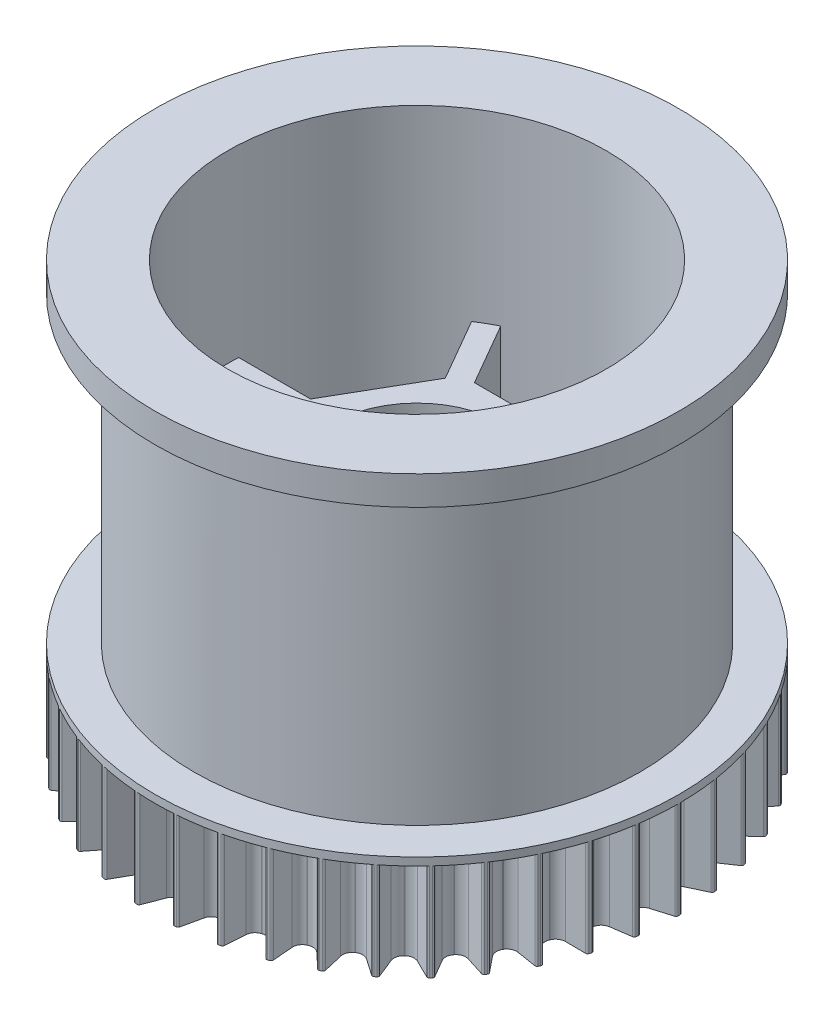
SolidWorks part; units mm, degrees
ref_plane "前视基准面" through (0, 0, 0) normal (0, 0, 1) x (1, 0, 0)
ref_plane "上视基准面" through (0, 0, 0) normal (0, 1, 0) x (1, 0, 0)
ref_plane "右视基准面" through (0, 0, 0) normal (1, 0, 0) x (0, 0, -1)
other "Configuration Table"
sketch "草图1" plane through (0, 0, 0) normal (0, 1, 0) x (1, 0, 0)
  line L0 (0, 0) -> (7.9279, 0) construction
  line L1 (0, 0) -> (0, 4.4256) construction
  line L2 (12.4216, 0.4494) -> (13.4287, 0.1463)
  line L3 (12.4216, -0.4494) -> (13.4287, -0.1463)
  line L4 (12.2159, -2.2957) -> (13.2569, -2.1461)
  line L5 (12.3499, -1.407) -> (13.3005, -1.8568)
  line L6 (11.7373, -4.0908) -> (12.789, -4.098)
  line L7 (12.0023, -3.2319) -> (12.8752, -3.8184)
  line L8 (10.9965, -5.7945) -> (12.0354, -5.9583)
  line L9 (11.3865, -4.9846) -> (12.1623, -5.6947)
  line L10 (10.0101, -7.3687) -> (11.0129, -7.6855)
  line L11 (10.5164, -6.626) -> (11.1777, -7.4438)
  line L12 (8.8, -8.7783) -> (9.7445, -9.2411)
  line L13 (9.4114, -8.1194) -> (9.9434, -9.0266)
  line L14 (7.3934, -9.9918) -> (8.2583, -10.5902)
  line L15 (8.0961, -9.4314) -> (8.487, -10.4078)
  line L16 (5.8216, -10.9822) -> (6.5877, -11.7028)
  line L17 (6.6, -10.5328) -> (6.841, -11.5565)
  line L18 (4.1198, -11.7272) -> (4.7699, -12.5539)
  line L19 (4.9565, -11.3988) -> (5.0422, -12.447)
  line L20 (2.3259, -12.2102) -> (2.8456, -13.1246)
  line L21 (3.2022, -12.0102) -> (3.1308, -13.0595)
  line L22 (0.4801, -12.4205) -> (0.8577, -13.4021)
  line L23 (1.3764, -12.3533) -> (1.1494, -13.3802)
  line L24 (-1.3764, -12.3533) -> (-1.1494, -13.3802)
  line L25 (-0.4801, -12.4205) -> (-0.8577, -13.4021)
  line L26 (-3.2022, -12.0102) -> (-3.1308, -13.0595)
  line L27 (-2.3259, -12.2102) -> (-2.8456, -13.1246)
  line L28 (-4.9565, -11.3988) -> (-5.0422, -12.447)
  line L29 (-4.1198, -11.7272) -> (-4.7699, -12.5539)
  line L30 (-6.6, -10.5328) -> (-6.841, -11.5565)
  line L31 (-5.8216, -10.9822) -> (-6.5877, -11.7028)
  line L32 (-8.0961, -9.4314) -> (-8.487, -10.4078)
  line L33 (-7.3934, -9.9918) -> (-8.2583, -10.5902)
  line L34 (-9.4114, -8.1194) -> (-9.9434, -9.0266)
  line L35 (-8.8, -8.7783) -> (-9.7445, -9.2411)
  line L36 (-10.5164, -6.626) -> (-11.1777, -7.4438)
  line L37 (-10.0101, -7.3687) -> (-11.0129, -7.6855)
  line L38 (-11.3865, -4.9846) -> (-12.1623, -5.6947)
  line L39 (-10.9965, -5.7945) -> (-12.0354, -5.9583)
  line L40 (-12.0023, -3.2319) -> (-12.8752, -3.8184)
  line L41 (-11.7373, -4.0908) -> (-12.789, -4.098)
  line L42 (-12.3499, -1.407) -> (-13.3005, -1.8568)
  line L43 (-12.2159, -2.2957) -> (-13.2569, -2.1461)
  line L44 (-12.4216, 0.4494) -> (-13.4287, 0.1463)
  line L45 (-12.4216, -0.4494) -> (-13.4287, -0.1463)
  line L46 (-12.2159, 2.2957) -> (-13.2569, 2.1461)
  line L47 (-12.3499, 1.407) -> (-13.3005, 1.8568)
  line L48 (-11.7373, 4.0908) -> (-12.789, 4.098)
  line L49 (-12.0023, 3.2319) -> (-12.8752, 3.8184)
  line L50 (-10.9965, 5.7945) -> (-12.0354, 5.9583)
  line L51 (-11.3865, 4.9846) -> (-12.1623, 5.6947)
  line L52 (-10.0101, 7.3687) -> (-11.0129, 7.6855)
  line L53 (-10.5164, 6.626) -> (-11.1777, 7.4438)
  line L54 (-8.8, 8.7783) -> (-9.7445, 9.2411)
  line L55 (-9.4114, 8.1194) -> (-9.9434, 9.0266)
  line L56 (-7.3934, 9.9918) -> (-8.2583, 10.5902)
  line L57 (-8.0961, 9.4314) -> (-8.487, 10.4078)
  line L58 (-5.8216, 10.9822) -> (-6.5877, 11.7028)
  line L59 (-6.6, 10.5328) -> (-6.841, 11.5565)
  line L60 (-4.1198, 11.7272) -> (-4.7699, 12.5539)
  line L61 (-4.9565, 11.3988) -> (-5.0422, 12.447)
  line L62 (-2.3259, 12.2102) -> (-2.8456, 13.1246)
  line L63 (-3.2022, 12.0102) -> (-3.1308, 13.0595)
  line L64 (-0.4801, 12.4205) -> (-0.8577, 13.4021)
  line L65 (-1.3764, 12.3533) -> (-1.1494, 13.3802)
  line L66 (1.3764, 12.3533) -> (1.1494, 13.3802)
  line L67 (0.4801, 12.4205) -> (0.8577, 13.4021)
  line L68 (3.2022, 12.0102) -> (3.1308, 13.0595)
  line L69 (2.3259, 12.2102) -> (2.8456, 13.1246)
  line L70 (4.9565, 11.3988) -> (5.0422, 12.447)
  line L71 (4.1198, 11.7272) -> (4.7699, 12.5539)
  line L72 (6.6, 10.5328) -> (6.841, 11.5565)
  line L73 (5.8216, 10.9822) -> (6.5877, 11.7028)
  line L74 (8.0961, 9.4314) -> (8.487, 10.4078)
  line L75 (7.3934, 9.9918) -> (8.2583, 10.5902)
  line L76 (9.4114, 8.1194) -> (9.9434, 9.0266)
  line L77 (8.8, 8.7783) -> (9.7445, 9.2411)
  line L78 (10.5164, 6.626) -> (11.1777, 7.4438)
  line L79 (10.0101, 7.3687) -> (11.0129, 7.6855)
  line L80 (11.3865, 4.9846) -> (12.1623, 5.6947)
  line L81 (10.9965, 5.7945) -> (12.0354, 5.9583)
  line L82 (12.0023, 3.2319) -> (12.8752, 3.8184)
  line L83 (11.7373, 4.0908) -> (12.789, 4.098)
  line L84 (12.3499, 1.407) -> (13.3005, 1.8568)
  line L85 (12.2159, 2.2957) -> (13.2569, 2.1461)
  line L95 (3.1754, 5.5) -> (-3.1754, 5.5) construction
  line L96 (3.1754, 5.5) -> (6.0333, 0.55) construction
  line L97 (0, 0) -> (3.1754, 5.5) construction
  line L98 (-3.1754, 5.5) -> (-6.0333, 0.55) construction
  line L99 (3.493, -4.95) -> (6.0333, -0.55)
  line L100 (2.5403, -5.5) -> (-2.5403, -5.5)
  line L101 (-3.493, -4.95) -> (-6.0333, -0.55)
  line L102 (8.1752, 0) -> (11.2, 0) construction
  line L103 (6.0333, 0.55) -> (11.1865, 0.55)
  line L104 (6.0333, -0.55) -> (11.1865, -0.55)
  line L105 (3.493, -4.95) -> (6.0696, -9.4128)
  line L106 (2.5403, -5.5) -> (5.1169, -9.9628)
  line L107 (-2.5403, -5.5) -> (-5.1169, -9.9628)
  line L108 (-3.493, -4.95) -> (-6.0696, -9.4128)
  line L109 (-6.0333, -0.55) -> (-11.1865, -0.55)
  line L110 (-6.0333, 0.55) -> (-11.1865, 0.55)
  line L111 (-3.493, 4.95) -> (-6.0696, 9.4128)
  line L112 (-2.5403, 5.5) -> (-5.1169, 9.9628)
  line L113 (2.5403, 5.5) -> (5.1169, 9.9628)
  line L114 (3.493, 4.95) -> (6.0696, 9.4128)
  line L115 (0, 0) -> (12.0337, 1.2648) construction
  line L116 (12.0337, -1.2648) -> (0, 0) construction
  line L117 (-6.0333, 0.55) -> (-3.493, 4.95)
  line L118 (-2.5403, 5.5) -> (2.5403, 5.5)
  line L119 (3.493, 4.95) -> (6.0333, 0.55)
  circle A0 centre (0, 0) radius 11.2 construction
  circle A1 centre (0, 0) radius 12.1 construction
  circle A2 centre (0, 0) radius 13.5 construction
  arc A3 (13.4999, 0.0509) -> (13.4999, -0.0509) centre (0, 0) cw
  arc A4 (12.0671, 0.8914) -> (12.0337, 1.2648) centre (0, 0) ccw construction
  arc A5 (13.4287, -0.1463) -> (13.4999, -0.0509) centre (13.3999, -0.0505) ccw
  arc A6 (13.4287, 0.1463) -> (13.4999, 0.0509) centre (13.3999, 0.0505) cw
  arc A7 (12.0671, -0.8914) -> (12.0337, -1.2648) centre (0, 0) cw construction
  arc A8 (12.4216, -0.4494) -> (12.0671, -0.8914) centre (12.5658, -0.9282) ccw
  arc A9 (12.4216, 0.4494) -> (12.0671, 0.8914) centre (12.5658, 0.9282) cw
  arc A10 (12.2159, -2.2957) -> (11.7995, -2.6799) centre (12.2871, -2.7907) ccw
  arc A11 (12.3499, -1.407) -> (12.0652, -0.9171) centre (12.5638, -0.955) cw
  arc A12 (13.3005, -1.8568) -> (13.3567, -1.9617) centre (13.2578, -1.9472) cw
  arc A13 (13.3567, -1.9617) -> (13.3415, -2.0624) centre (0, 0) cw
  arc A14 (13.2569, -2.1461) -> (13.3415, -2.0624) centre (13.2427, -2.0471) ccw
  arc A15 (11.7373, -4.0908) -> (11.2683, -4.4086) centre (11.7339, -4.5908) ccw
  arc A16 (12.0023, -3.2319) -> (11.7937, -2.7051) centre (12.2811, -2.8169) cw
  arc A17 (12.8752, -3.8184) -> (12.9151, -3.9305) centre (12.8195, -3.9014) cw
  arc A18 (12.9151, -3.9305) -> (12.8851, -4.0278) centre (0, 0) cw
  arc A19 (12.789, -4.098) -> (12.8851, -4.0278) centre (12.7897, -3.998) ccw
  arc A20 (10.9965, -5.7945) -> (10.4854, -6.0388) centre (10.9186, -6.2884) ccw
  arc A21 (11.3865, -4.9846) -> (11.2589, -4.4326) centre (11.7241, -4.6158) cw
  arc A22 (12.1623, -5.6947) -> (12.1851, -5.8115) centre (12.0948, -5.7685) cw
  arc A23 (12.1851, -5.8115) -> (12.1409, -5.9032) centre (0, 0) cw
  arc A24 (12.0354, -5.9583) -> (12.1409, -5.9032) centre (12.051, -5.8595) ccw
  arc A25 (10.0101, -7.3687) -> (9.4682, -7.5341) centre (9.8595, -7.8455) ccw
  arc A26 (10.5164, -6.626) -> (10.4724, -6.0612) centre (10.9052, -6.3116) cw
  arc A27 (11.1777, -7.4438) -> (11.1828, -7.5627) centre (11.1, -7.5067) cw
  arc A28 (11.1828, -7.5627) -> (11.1255, -7.6468) centre (0, 0) cw
  arc A29 (11.0129, -7.6855) -> (11.1255, -7.6468) centre (11.0431, -7.5902) ccw
  arc A30 (8.8, -8.7783) -> (8.2395, -8.8611) centre (8.58, -9.2273) ccw
  arc A31 (9.4114, -8.1194) -> (9.4521, -7.5543) centre (9.8427, -7.8665) cw
  arc A32 (9.9434, -9.0266) -> (9.9308, -9.145) centre (9.8572, -9.0772) cw
  arc A33 (9.9308, -9.145) -> (9.8615, -9.2196) centre (0, 0) cw
  arc A34 (9.7445, -9.2411) -> (9.8615, -9.2196) centre (9.7885, -9.1513) ccw
  arc A35 (7.3934, -9.9918) -> (6.8268, -9.9902) centre (7.1089, -10.403) ccw
  arc A36 (8.0961, -9.4314) -> (8.2206, -8.8787) centre (8.5603, -9.2456) cw
  arc A37 (8.487, -10.4078) -> (8.4568, -10.5229) centre (8.3942, -10.445) cw
  arc A38 (8.4568, -10.5229) -> (8.3773, -10.5864) centre (0, 0) cw
  arc A39 (8.2583, -10.5902) -> (8.3773, -10.5864) centre (8.3152, -10.508) ccw
  arc A40 (5.8216, -10.9822) -> (5.2616, -10.8961) centre (5.479, -11.3464) ccw
  arc A41 (6.6, -10.5328) -> (6.8055, -10.0048) centre (7.0867, -10.4182) cw
  arc A42 (6.841, -11.5565) -> (6.794, -11.6658) centre (6.7437, -11.5794) cw
  arc A43 (6.794, -11.6658) -> (6.7059, -11.7167) centre (0, 0) cw
  arc A44 (6.5877, -11.7028) -> (6.7059, -11.7167) centre (6.6562, -11.6299) ccw
  arc A45 (4.1198, -11.7272) -> (3.5789, -11.5586) centre (3.7268, -12.0362) ccw
  arc A46 (4.9565, -11.3988) -> (5.2384, -10.9073) centre (5.4548, -11.358) cw
  arc A47 (5.0422, -12.447) -> (4.9795, -12.5481) centre (4.9426, -12.4552) cw
  arc A48 (4.9795, -12.5481) -> (4.8847, -12.5853) centre (0, 0) cw
  arc A49 (4.7699, -12.5539) -> (4.8847, -12.5853) centre (4.8485, -12.4921) ccw
  arc A50 (2.3259, -12.2102) -> (1.8162, -11.9629) centre (1.8912, -12.4573) ccw
  arc A51 (3.2022, -12.0102) -> (3.5542, -11.5662) centre (3.7011, -12.0442) cw
  arc A52 (3.1308, -13.0595) -> (3.0536, -13.1501) centre (3.031, -13.0527) cw
  arc A53 (3.0536, -13.1501) -> (2.9544, -13.1728) centre (0, 0) cw
  arc A54 (2.8456, -13.1246) -> (2.9544, -13.1728) centre (2.9325, -13.0752) ccw
  arc A55 (0.4801, -12.4205) -> (0.0129, -12.1) centre (0.0134, -12.6) ccw
  arc A56 (1.3764, -12.3533) -> (1.7906, -11.9668) centre (1.8646, -12.4613) cw
  arc A57 (1.1494, -13.3802) -> (1.0596, -13.4584) centre (1.0518, -13.3587) cw
  arc A58 (1.0596, -13.4584) -> (0.9581, -13.466) centre (0, 0) cw
  arc A59 (0.8577, -13.4021) -> (0.9581, -13.466) centre (0.951, -13.3662) ccw
  arc A60 (-1.3764, -12.3533) -> (-1.7906, -11.9668) centre (-1.8646, -12.4613) ccw
  arc A61 (-0.4801, -12.4205) -> (-0.0129, -12.1) centre (-0.0134, -12.6) cw
  arc A62 (-0.8577, -13.4021) -> (-0.9581, -13.466) centre (-0.951, -13.3662) cw
  arc A63 (-0.9581, -13.466) -> (-1.0596, -13.4584) centre (0, 0) cw
  arc A64 (-1.1494, -13.3802) -> (-1.0596, -13.4584) centre (-1.0518, -13.3587) ccw
  arc A65 (-3.2022, -12.0102) -> (-3.5542, -11.5662) centre (-3.7011, -12.0442) ccw
  arc A66 (-2.3259, -12.2102) -> (-1.8162, -11.9629) centre (-1.8912, -12.4573) cw
  arc A67 (-2.8456, -13.1246) -> (-2.9544, -13.1728) centre (-2.9325, -13.0752) cw
  arc A68 (-2.9544, -13.1728) -> (-3.0536, -13.1501) centre (0, 0) cw
  arc A69 (-3.1308, -13.0595) -> (-3.0536, -13.1501) centre (-3.031, -13.0527) ccw
  arc A70 (-4.9565, -11.3988) -> (-5.2384, -10.9073) centre (-5.4548, -11.358) ccw
  arc A71 (-4.1198, -11.7272) -> (-3.5789, -11.5586) centre (-3.7268, -12.0362) cw
  arc A72 (-4.7699, -12.5539) -> (-4.8847, -12.5853) centre (-4.8485, -12.4921) cw
  arc A73 (-4.8847, -12.5853) -> (-4.9795, -12.5481) centre (0, 0) cw
  arc A74 (-5.0422, -12.447) -> (-4.9795, -12.5481) centre (-4.9426, -12.4552) ccw
  arc A75 (-6.6, -10.5328) -> (-6.8055, -10.0048) centre (-7.0867, -10.4182) ccw
  arc A76 (-5.8216, -10.9822) -> (-5.2616, -10.8961) centre (-5.479, -11.3464) cw
  arc A77 (-6.5877, -11.7028) -> (-6.7059, -11.7167) centre (-6.6562, -11.6299) cw
  arc A78 (-6.7059, -11.7167) -> (-6.794, -11.6658) centre (0, 0) cw
  arc A79 (-6.841, -11.5565) -> (-6.794, -11.6658) centre (-6.7437, -11.5794) ccw
  arc A80 (-8.0961, -9.4314) -> (-8.2206, -8.8787) centre (-8.5603, -9.2456) ccw
  arc A81 (-7.3934, -9.9918) -> (-6.8268, -9.9902) centre (-7.1089, -10.403) cw
  arc A82 (-8.2583, -10.5902) -> (-8.3773, -10.5864) centre (-8.3152, -10.508) cw
  arc A83 (-8.3773, -10.5864) -> (-8.4568, -10.5229) centre (0, 0) cw
  arc A84 (-8.487, -10.4078) -> (-8.4568, -10.5229) centre (-8.3942, -10.445) ccw
  arc A85 (-9.4114, -8.1194) -> (-9.4521, -7.5543) centre (-9.8427, -7.8665) ccw
  arc A86 (-8.8, -8.7783) -> (-8.2395, -8.8611) centre (-8.58, -9.2273) cw
  arc A87 (-9.7445, -9.2411) -> (-9.8615, -9.2196) centre (-9.7885, -9.1513) cw
  arc A88 (-9.8615, -9.2196) -> (-9.9308, -9.145) centre (0, 0) cw
  arc A89 (-9.9434, -9.0266) -> (-9.9308, -9.145) centre (-9.8572, -9.0772) ccw
  arc A90 (-10.5164, -6.626) -> (-10.4724, -6.0612) centre (-10.9052, -6.3116) ccw
  arc A91 (-10.0101, -7.3687) -> (-9.4682, -7.5341) centre (-9.8595, -7.8455) cw
  arc A92 (-11.0129, -7.6855) -> (-11.1255, -7.6468) centre (-11.0431, -7.5902) cw
  arc A93 (-11.1255, -7.6468) -> (-11.1828, -7.5627) centre (0, 0) cw
  arc A94 (-11.1777, -7.4438) -> (-11.1828, -7.5627) centre (-11.1, -7.5067) ccw
  arc A95 (-11.3865, -4.9846) -> (-11.2589, -4.4326) centre (-11.7241, -4.6158) ccw
  arc A96 (-10.9965, -5.7945) -> (-10.4854, -6.0388) centre (-10.9186, -6.2884) cw
  arc A97 (-12.0354, -5.9583) -> (-12.1409, -5.9032) centre (-12.051, -5.8595) cw
  arc A98 (-12.1409, -5.9032) -> (-12.1851, -5.8115) centre (0, 0) cw
  arc A99 (-12.1623, -5.6947) -> (-12.1851, -5.8115) centre (-12.0948, -5.7685) ccw
  arc A100 (-12.0023, -3.2319) -> (-11.7937, -2.7051) centre (-12.2811, -2.8169) ccw
  arc A101 (-11.7373, -4.0908) -> (-11.2683, -4.4086) centre (-11.7339, -4.5908) cw
  arc A102 (-12.789, -4.098) -> (-12.8851, -4.0278) centre (-12.7897, -3.998) cw
  arc A103 (-12.8851, -4.0278) -> (-12.9151, -3.9305) centre (0, 0) cw
  arc A104 (-12.8752, -3.8184) -> (-12.9151, -3.9305) centre (-12.8195, -3.9014) ccw
  arc A105 (-12.3499, -1.407) -> (-12.0652, -0.9171) centre (-12.5638, -0.955) ccw
  arc A106 (-12.2159, -2.2957) -> (-11.7995, -2.6799) centre (-12.2871, -2.7907) cw
  arc A107 (-13.2569, -2.1461) -> (-13.3415, -2.0624) centre (-13.2427, -2.0471) cw
  arc A108 (-13.3415, -2.0624) -> (-13.3567, -1.9617) centre (0, 0) cw
  arc A109 (-13.3005, -1.8568) -> (-13.3567, -1.9617) centre (-13.2578, -1.9472) ccw
  arc A110 (-12.4216, 0.4494) -> (-12.0671, 0.8914) centre (-12.5658, 0.9282) ccw
  arc A111 (-12.4216, -0.4494) -> (-12.0671, -0.8914) centre (-12.5658, -0.9282) cw
  arc A112 (-13.4287, -0.1463) -> (-13.4999, -0.0509) centre (-13.3999, -0.0505) cw
  arc A113 (-13.4999, -0.0509) -> (-13.4999, 0.0509) centre (0, 0) cw
  arc A114 (-13.4287, 0.1463) -> (-13.4999, 0.0509) centre (-13.3999, 0.0505) ccw
  arc A115 (-12.2159, 2.2957) -> (-11.7995, 2.6799) centre (-12.2871, 2.7907) ccw
  arc A116 (-12.3499, 1.407) -> (-12.0652, 0.9171) centre (-12.5638, 0.955) cw
  arc A117 (-13.3005, 1.8568) -> (-13.3567, 1.9617) centre (-13.2578, 1.9472) cw
  arc A118 (-13.3567, 1.9617) -> (-13.3415, 2.0624) centre (0, 0) cw
  arc A119 (-13.2569, 2.1461) -> (-13.3415, 2.0624) centre (-13.2427, 2.0471) ccw
  arc A120 (-11.7373, 4.0908) -> (-11.2683, 4.4086) centre (-11.7339, 4.5908) ccw
  arc A121 (-12.0023, 3.2319) -> (-11.7937, 2.7051) centre (-12.2811, 2.8169) cw
  arc A122 (-12.8752, 3.8184) -> (-12.9151, 3.9305) centre (-12.8195, 3.9014) cw
  arc A123 (-12.9151, 3.9305) -> (-12.8851, 4.0278) centre (0, 0) cw
  arc A124 (-12.789, 4.098) -> (-12.8851, 4.0278) centre (-12.7897, 3.998) ccw
  arc A125 (-10.9965, 5.7945) -> (-10.4854, 6.0388) centre (-10.9186, 6.2884) ccw
  arc A126 (-11.3865, 4.9846) -> (-11.2589, 4.4326) centre (-11.7241, 4.6158) cw
  arc A127 (-12.1623, 5.6947) -> (-12.1851, 5.8115) centre (-12.0948, 5.7685) cw
  arc A128 (-12.1851, 5.8115) -> (-12.1409, 5.9032) centre (0, 0) cw
  arc A129 (-12.0354, 5.9583) -> (-12.1409, 5.9032) centre (-12.051, 5.8595) ccw
  arc A130 (-10.0101, 7.3687) -> (-9.4682, 7.5341) centre (-9.8595, 7.8455) ccw
  arc A131 (-10.5164, 6.626) -> (-10.4724, 6.0612) centre (-10.9052, 6.3116) cw
  arc A132 (-11.1777, 7.4438) -> (-11.1828, 7.5627) centre (-11.1, 7.5067) cw
  arc A133 (-11.1828, 7.5627) -> (-11.1255, 7.6468) centre (0, 0) cw
  arc A134 (-11.0129, 7.6855) -> (-11.1255, 7.6468) centre (-11.0431, 7.5902) ccw
  arc A135 (-8.8, 8.7783) -> (-8.2395, 8.8611) centre (-8.58, 9.2273) ccw
  arc A136 (-9.4114, 8.1194) -> (-9.4521, 7.5543) centre (-9.8427, 7.8665) cw
  arc A137 (-9.9434, 9.0266) -> (-9.9308, 9.145) centre (-9.8572, 9.0772) cw
  arc A138 (-9.9308, 9.145) -> (-9.8615, 9.2196) centre (0, 0) cw
  arc A139 (-9.7445, 9.2411) -> (-9.8615, 9.2196) centre (-9.7885, 9.1513) ccw
  arc A140 (-7.3934, 9.9918) -> (-6.8268, 9.9902) centre (-7.1089, 10.403) ccw
  arc A141 (-8.0961, 9.4314) -> (-8.2206, 8.8787) centre (-8.5603, 9.2456) cw
  arc A142 (-8.487, 10.4078) -> (-8.4568, 10.5229) centre (-8.3942, 10.445) cw
  arc A143 (-8.4568, 10.5229) -> (-8.3773, 10.5864) centre (0, 0) cw
  arc A144 (-8.2583, 10.5902) -> (-8.3773, 10.5864) centre (-8.3152, 10.508) ccw
  arc A145 (-5.8216, 10.9822) -> (-5.2616, 10.8961) centre (-5.479, 11.3464) ccw
  arc A146 (-6.6, 10.5328) -> (-6.8055, 10.0048) centre (-7.0867, 10.4182) cw
  arc A147 (-6.841, 11.5565) -> (-6.794, 11.6658) centre (-6.7437, 11.5794) cw
  arc A148 (-6.794, 11.6658) -> (-6.7059, 11.7167) centre (0, 0) cw
  arc A149 (-6.5877, 11.7028) -> (-6.7059, 11.7167) centre (-6.6562, 11.6299) ccw
  arc A150 (-4.1198, 11.7272) -> (-3.5789, 11.5586) centre (-3.7268, 12.0362) ccw
  arc A151 (-4.9565, 11.3988) -> (-5.2384, 10.9073) centre (-5.4548, 11.358) cw
  arc A152 (-5.0422, 12.447) -> (-4.9795, 12.5481) centre (-4.9426, 12.4552) cw
  arc A153 (-4.9795, 12.5481) -> (-4.8847, 12.5853) centre (0, 0) cw
  arc A154 (-4.7699, 12.5539) -> (-4.8847, 12.5853) centre (-4.8485, 12.4921) ccw
  arc A155 (-2.3259, 12.2102) -> (-1.8162, 11.9629) centre (-1.8912, 12.4573) ccw
  arc A156 (-3.2022, 12.0102) -> (-3.5542, 11.5662) centre (-3.7011, 12.0442) cw
  arc A157 (-3.1308, 13.0595) -> (-3.0536, 13.1501) centre (-3.031, 13.0527) cw
  arc A158 (-3.0536, 13.1501) -> (-2.9544, 13.1728) centre (0, 0) cw
  arc A159 (-2.8456, 13.1246) -> (-2.9544, 13.1728) centre (-2.9325, 13.0752) ccw
  arc A160 (-0.4801, 12.4205) -> (-0.0129, 12.1) centre (-0.0134, 12.6) ccw
  arc A161 (-1.3764, 12.3533) -> (-1.7906, 11.9668) centre (-1.8646, 12.4613) cw
  arc A162 (-1.1494, 13.3802) -> (-1.0596, 13.4584) centre (-1.0518, 13.3587) cw
  arc A163 (-1.0596, 13.4584) -> (-0.9581, 13.466) centre (0, 0) cw
  arc A164 (-0.8577, 13.4021) -> (-0.9581, 13.466) centre (-0.951, 13.3662) ccw
  arc A165 (1.3764, 12.3533) -> (1.7906, 11.9668) centre (1.8646, 12.4613) ccw
  arc A166 (0.4801, 12.4205) -> (0.0129, 12.1) centre (0.0134, 12.6) cw
  arc A167 (0.8577, 13.4021) -> (0.9581, 13.466) centre (0.951, 13.3662) cw
  arc A168 (0.9581, 13.466) -> (1.0596, 13.4584) centre (0, 0) cw
  arc A169 (1.1494, 13.3802) -> (1.0596, 13.4584) centre (1.0518, 13.3587) ccw
  arc A170 (3.2022, 12.0102) -> (3.5542, 11.5662) centre (3.7011, 12.0442) ccw
  arc A171 (2.3259, 12.2102) -> (1.8162, 11.9629) centre (1.8912, 12.4573) cw
  arc A172 (2.8456, 13.1246) -> (2.9544, 13.1728) centre (2.9325, 13.0752) cw
  arc A173 (2.9544, 13.1728) -> (3.0536, 13.1501) centre (0, 0) cw
  arc A174 (3.1308, 13.0595) -> (3.0536, 13.1501) centre (3.031, 13.0527) ccw
  arc A175 (4.9565, 11.3988) -> (5.2384, 10.9073) centre (5.4548, 11.358) ccw
  arc A176 (4.1198, 11.7272) -> (3.5789, 11.5586) centre (3.7268, 12.0362) cw
  arc A177 (4.7699, 12.5539) -> (4.8847, 12.5853) centre (4.8485, 12.4921) cw
  arc A178 (4.8847, 12.5853) -> (4.9795, 12.5481) centre (0, 0) cw
  arc A179 (5.0422, 12.447) -> (4.9795, 12.5481) centre (4.9426, 12.4552) ccw
  arc A180 (6.6, 10.5328) -> (6.8055, 10.0048) centre (7.0867, 10.4182) ccw
  arc A181 (5.8216, 10.9822) -> (5.2616, 10.8961) centre (5.479, 11.3464) cw
  arc A182 (6.5877, 11.7028) -> (6.7059, 11.7167) centre (6.6562, 11.6299) cw
  arc A183 (6.7059, 11.7167) -> (6.794, 11.6658) centre (0, 0) cw
  arc A184 (6.841, 11.5565) -> (6.794, 11.6658) centre (6.7437, 11.5794) ccw
  arc A185 (8.0961, 9.4314) -> (8.2206, 8.8787) centre (8.5603, 9.2456) ccw
  arc A186 (7.3934, 9.9918) -> (6.8268, 9.9902) centre (7.1089, 10.403) cw
  arc A187 (8.2583, 10.5902) -> (8.3773, 10.5864) centre (8.3152, 10.508) cw
  arc A188 (8.3773, 10.5864) -> (8.4568, 10.5229) centre (0, 0) cw
  arc A189 (8.487, 10.4078) -> (8.4568, 10.5229) centre (8.3942, 10.445) ccw
  arc A190 (9.4114, 8.1194) -> (9.4521, 7.5543) centre (9.8427, 7.8665) ccw
  arc A191 (8.8, 8.7783) -> (8.2395, 8.8611) centre (8.58, 9.2273) cw
  arc A192 (9.7445, 9.2411) -> (9.8615, 9.2196) centre (9.7885, 9.1513) cw
  arc A193 (9.8615, 9.2196) -> (9.9308, 9.145) centre (0, 0) cw
  arc A194 (9.9434, 9.0266) -> (9.9308, 9.145) centre (9.8572, 9.0772) ccw
  arc A195 (10.5164, 6.626) -> (10.4724, 6.0612) centre (10.9052, 6.3116) ccw
  arc A196 (10.0101, 7.3687) -> (9.4682, 7.5341) centre (9.8595, 7.8455) cw
  arc A197 (11.0129, 7.6855) -> (11.1255, 7.6468) centre (11.0431, 7.5902) cw
  arc A198 (11.1255, 7.6468) -> (11.1828, 7.5627) centre (0, 0) cw
  arc A199 (11.1777, 7.4438) -> (11.1828, 7.5627) centre (11.1, 7.5067) ccw
  arc A200 (11.3865, 4.9846) -> (11.2589, 4.4326) centre (11.7241, 4.6158) ccw
  arc A201 (10.9965, 5.7945) -> (10.4854, 6.0388) centre (10.9186, 6.2884) cw
  arc A202 (12.0354, 5.9583) -> (12.1409, 5.9032) centre (12.051, 5.8595) cw
  arc A203 (12.1409, 5.9032) -> (12.1851, 5.8115) centre (0, 0) cw
  arc A204 (12.1623, 5.6947) -> (12.1851, 5.8115) centre (12.0948, 5.7685) ccw
  arc A205 (12.0023, 3.2319) -> (11.7937, 2.7051) centre (12.2811, 2.8169) ccw
  arc A206 (11.7373, 4.0908) -> (11.2683, 4.4086) centre (11.7339, 4.5908) cw
  arc A207 (12.789, 4.098) -> (12.8851, 4.0278) centre (12.7897, 3.998) cw
  arc A208 (12.8851, 4.0278) -> (12.9151, 3.9305) centre (0, 0) cw
  arc A209 (12.8752, 3.8184) -> (12.9151, 3.9305) centre (12.8195, 3.9014) ccw
  arc A210 (12.3499, 1.407) -> (12.0652, 0.9171) centre (12.5638, 0.955) ccw
  arc A211 (12.2159, 2.2957) -> (11.7995, 2.6799) centre (12.2871, 2.7907) cw
  arc A212 (13.2569, 2.1461) -> (13.3415, 2.0624) centre (13.2427, 2.0471) cw
  arc A213 (13.3415, 2.0624) -> (13.3567, 1.9617) centre (0, 0) cw
  arc A214 (13.3005, 1.8568) -> (13.3567, 1.9617) centre (13.2578, 1.9472) ccw
  circle A216 centre (0, 0) radius 4.4
  arc A217 (11.1865, 0.55) -> (6.0696, 9.4128) centre (0, 0) ccw
  arc A218 (5.1169, 9.9628) -> (-5.1169, 9.9628) centre (0, 0) ccw
  arc A219 (-6.0696, 9.4128) -> (-11.1865, 0.55) centre (0, 0) ccw
  arc A220 (-11.1865, -0.55) -> (-6.0696, -9.4128) centre (0, 0) ccw
  arc A221 (-5.1169, -9.9628) -> (5.1169, -9.9628) centre (0, 0) ccw
  arc A222 (6.0696, -9.4128) -> (11.1865, -0.55) centre (0, 0) ccw
  arc A223 (12.0652, 0.9171) -> (12.0671, 0.8914) centre (0, 0) cw
  arc A224 (12.0671, -0.8914) -> (12.0652, -0.9171) centre (0, 0) cw
  arc A225 (11.7995, -2.6799) -> (11.7937, -2.7051) centre (0, 0) cw
  arc A226 (11.2683, -4.4086) -> (11.2589, -4.4326) centre (0, 0) cw
  arc A227 (10.4854, -6.0388) -> (10.4724, -6.0612) centre (0, 0) cw
  arc A228 (9.4682, -7.5341) -> (9.4521, -7.5543) centre (0, 0) cw
  arc A229 (8.2395, -8.8611) -> (8.2206, -8.8787) centre (0, 0) cw
  arc A230 (6.8268, -9.9902) -> (6.8055, -10.0048) centre (0, 0) cw
  arc A231 (5.2616, -10.8961) -> (5.2384, -10.9073) centre (0, 0) cw
  arc A232 (3.5789, -11.5586) -> (3.5542, -11.5662) centre (0, 0) cw
  arc A233 (1.8162, -11.9629) -> (1.7906, -11.9668) centre (0, 0) cw
  arc A234 (0.0129, -12.1) -> (-0.0129, -12.1) centre (0, 0) cw
  arc A235 (-1.7906, -11.9668) -> (-1.8162, -11.9629) centre (0, 0) cw
  arc A236 (-3.5542, -11.5662) -> (-3.5789, -11.5586) centre (0, 0) cw
  arc A237 (-5.2384, -10.9073) -> (-5.2616, -10.8961) centre (0, 0) cw
  arc A238 (-6.8055, -10.0048) -> (-6.8268, -9.9902) centre (0, 0) cw
  arc A239 (-8.2206, -8.8787) -> (-8.2395, -8.8611) centre (0, 0) cw
  arc A240 (-9.4521, -7.5543) -> (-9.4682, -7.5341) centre (0, 0) cw
  arc A241 (-10.4724, -6.0612) -> (-10.4854, -6.0388) centre (0, 0) cw
  arc A242 (-11.2589, -4.4326) -> (-11.2683, -4.4086) centre (0, 0) cw
  arc A243 (-11.7937, -2.7051) -> (-11.7995, -2.6799) centre (0, 0) cw
  arc A244 (-12.0652, -0.9171) -> (-12.0671, -0.8914) centre (0, 0) cw
  arc A245 (-12.0671, 0.8914) -> (-12.0652, 0.9171) centre (0, 0) cw
  arc A246 (-11.7995, 2.6799) -> (-11.7937, 2.7051) centre (0, 0) cw
  arc A247 (-11.2683, 4.4086) -> (-11.2589, 4.4326) centre (0, 0) cw
  arc A248 (-10.4854, 6.0388) -> (-10.4724, 6.0612) centre (0, 0) cw
  arc A249 (-9.4682, 7.5341) -> (-9.4521, 7.5543) centre (0, 0) cw
  arc A250 (-8.2395, 8.8611) -> (-8.2206, 8.8787) centre (0, 0) cw
  arc A251 (-6.8268, 9.9902) -> (-6.8055, 10.0048) centre (0, 0) cw
  arc A252 (-5.2616, 10.8961) -> (-5.2384, 10.9073) centre (0, 0) cw
  arc A253 (-3.5789, 11.5586) -> (-3.5542, 11.5662) centre (0, 0) cw
  arc A254 (-1.8162, 11.9629) -> (-1.7906, 11.9668) centre (0, 0) cw
  arc A255 (-0.0129, 12.1) -> (0.0129, 12.1) centre (0, 0) cw
  arc A256 (1.7906, 11.9668) -> (1.8162, 11.9629) centre (0, 0) cw
  arc A257 (3.5542, 11.5662) -> (3.5789, 11.5586) centre (0, 0) cw
  arc A258 (5.2384, 10.9073) -> (5.2616, 10.8961) centre (0, 0) cw
  arc A259 (6.8055, 10.0048) -> (6.8268, 9.9902) centre (0, 0) cw
  arc A260 (8.2206, 8.8787) -> (8.2395, 8.8611) centre (0, 0) cw
  arc A261 (9.4521, 7.5543) -> (9.4682, 7.5341) centre (0, 0) cw
  arc A262 (10.4724, 6.0612) -> (10.4854, 6.0388) centre (0, 0) cw
  arc A263 (11.2589, 4.4326) -> (11.2683, 4.4086) centre (0, 0) cw
  arc A264 (11.7937, 2.7051) -> (11.7995, 2.6799) centre (0, 0) cw
  circle A265 centre (0, 0) radius 3.5
  point P17 (13.4994, -0.125)
  point P20 (13.4994, 0.125)
  point P23 (12.0875, -0.55)
  point P26 (12.0875, 0.55)
  point P524 (0, 5.5)
  dimension "D1" = 22.4
  dimension "D2" = 24.2
  dimension "D3" = 27
  dimension "D6" = 0.1
  dimension "D7" = 0.5
  dimension "D9" = 120
  dimension "D12" = 8.8
  dimension "D14" = 7
  dimension "D4" = 1.1
  dimension "D5" = 0.25
  dimension "D10" = 5.5
  dimension "D11" = 30
  dimension "D16" = 6
  dimension "D17" = 6
  dimension "D8" = 42
  dimension "D13" = 6
  dimension "D15" = 42
extrude "凸台-拉伸1" add sketch "草图1" along normal blind 5 contours A264 A205 L82 A209 A208 A207 L83 A206 A263 A200 L80 A204 A203 A202 L81 A201 A262 A195 L78 A199 A198 A197 L79 A196 A261 A190 L76 A194 A193 A192 L77 A191 A260 A185 L74 A189 A188 A187 L75 A186 A259 A180 L72 A184 A183 A182 L73 A181 A258 A175 L70 region at (12.8153, 0, 0.0673)
sketch "草图2" plane through (0, 5, 0) normal (0, 1, 0) x (1, 0, 0)
  circle A0 centre (0, 0) radius 13.5
  circle A2 centre (0, 0) radius 11.2
  arc A4 (11.1865, 0.55) -> (6.0696, 9.4128) centre (0, 0) ccw construction
  dimension "D1" = 27
extrude "凸台-拉伸2" add sketch "草图2" along normal blind 0.4 contours A0 A2 | A2 | A0 region at (-13.1182, 5, 0)
extrude "拉伸-薄壁2" add sketch "草图2<2>" along normal blind 16 thin contours A2 thin type mid plane wall 0.6
sketch "草图2<2>" plane through (0, 5, 0) normal (0, 1, 0) x (1, 0, 0) same geometry as "草图2"
sketch "草图5" plane through (0, 21, 0) normal (0, 1, 0) x (1, 0, 0)
  circle A0 centre (0, 0) radius 13.5
  circle A2 centre (0, 0) radius 10.9
  circle A3 centre (0, 0) radius 10.9 construction
  dimension "D1" = 27
extrude "凸台-拉伸3" add sketch "草图5" along normal blind 1.5
sketch "草图6" plane through (0, 5, 0) normal (0, 1, 0) x (1, 0, 0)
  line L18 (-4.9667, -9.7027) -> (-2.5403, -5.5)
  line L19 (-2.5403, -5.5) -> (2.5403, -5.5)
  line L20 (2.5403, -5.5) -> (4.9667, -9.7027)
  line L21 (5.9194, -9.1527) -> (3.493, -4.95)
  line L22 (3.493, -4.95) -> (6.0333, -0.55)
  line L23 (6.0333, -0.55) -> (10.8861, -0.55)
  line L24 (10.8861, 0.55) -> (6.0333, 0.55)
  line L25 (6.0333, 0.55) -> (3.493, 4.95)
  line L26 (3.493, 4.95) -> (5.9194, 9.1527)
  line L27 (4.9667, 9.7027) -> (2.5403, 5.5)
  line L28 (2.5403, 5.5) -> (-2.5403, 5.5)
  line L29 (-2.5403, 5.5) -> (-4.9667, 9.7027)
  line L30 (-5.9194, 9.1527) -> (-3.493, 4.95)
  line L31 (-3.493, 4.95) -> (-6.0333, 0.55)
  line L32 (-6.0333, 0.55) -> (-10.8861, 0.55)
  line L33 (-10.8861, -0.55) -> (-6.0333, -0.55)
  line L34 (-6.0333, -0.55) -> (-3.493, -4.95)
  line L35 (-3.493, -4.95) -> (-5.9194, -9.1527)
  line L36 (-4.9667, -9.7027) -> (-2.5403, -5.5)
  line L37 (-2.5403, -5.5) -> (2.5403, -5.5)
  line L38 (2.5403, -5.5) -> (4.9667, -9.7027)
  line L39 (5.9194, -9.1527) -> (3.493, -4.95)
  line L40 (3.493, -4.95) -> (6.0333, -0.55)
  line L41 (6.0333, -0.55) -> (10.8861, -0.55)
  line L42 (10.8861, 0.55) -> (6.0333, 0.55)
  line L43 (6.0333, 0.55) -> (3.493, 4.95)
  line L44 (3.493, 4.95) -> (5.9194, 9.1527)
  line L45 (4.9667, 9.7027) -> (2.5403, 5.5)
  line L46 (2.5403, 5.5) -> (-2.5403, 5.5)
  line L47 (-2.5403, 5.5) -> (-4.9667, 9.7027)
  line L48 (-5.9194, 9.1527) -> (-3.493, 4.95)
  line L49 (-3.493, 4.95) -> (-6.0333, 0.55)
  line L50 (-6.0333, 0.55) -> (-10.8861, 0.55)
  line L51 (-10.8861, -0.55) -> (-6.0333, -0.55)
  line L52 (-6.0333, -0.55) -> (-3.493, -4.95)
  line L53 (-3.493, -4.95) -> (-5.9194, -9.1527)
  circle A0 centre (0, 0) radius 4.4
  circle A1 centre (0, 0) radius 4.4 construction
  arc A6 (-5.9194, -9.1527) -> (-4.9667, -9.7027) centre (0, 0) ccw
  arc A7 (4.9667, -9.7027) -> (5.9194, -9.1527) centre (0, 0) ccw
  arc A8 (10.8861, -0.55) -> (10.8861, 0.55) centre (0, 0) ccw
  arc A9 (5.9194, 9.1527) -> (4.9667, 9.7027) centre (0, 0) ccw
  arc A10 (-4.9667, 9.7027) -> (-5.9194, 9.1527) centre (0, 0) ccw
  arc A11 (-10.8861, 0.55) -> (-10.8861, -0.55) centre (0, 0) ccw
  arc A12 (-5.9194, -9.1527) -> (-4.9667, -9.7027) centre (0, 0) ccw
  arc A13 (4.9667, -9.7027) -> (5.9194, -9.1527) centre (0, 0) ccw
  arc A14 (10.8861, -0.55) -> (10.8861, 0.55) centre (0, 0) ccw
  arc A15 (5.9194, 9.1527) -> (4.9667, 9.7027) centre (0, 0) ccw
  arc A16 (-4.9667, 9.7027) -> (-5.9194, 9.1527) centre (0, 0) ccw
  arc A17 (-10.8861, 0.55) -> (-10.8861, -0.55) centre (0, 0) ccw
  dimension "D1" = 0
extrude "凸台-拉伸4" add sketch "草图6" along normal blind 8
extrude "凸台-拉伸5" add sketch "草图1<6>" along normal up to surface (13 mm away) contours A216 A265 region at (-4.2755, 0, 0) up to face at (0, 13, 0)
sketch "草图1<6>" plane through (0, 0, 0) normal (0, 1, 0) x (1, 0, 0) same geometry as "草图1"
extrude "切除-拉伸1" cut sketch "草图1<7>" along normal blind 3 contours A216 A265 region at (-4.2755, 0, 0)
sketch "草图1<7>" plane through (0, 0, 0) normal (0, 1, 0) x (1, 0, 0) same geometry as "草图1"
sketch "草图8" plane through (0, 13, 0) normal (0, 1, 0) x (1, 0, 0)
  circle A0 centre (0, 0) radius 4.4
  circle A1 centre (0, 0) radius 3.5
  circle A4 centre (0, 0) radius 3.5 construction
  dimension "D1" = 8.8
extrude "切除-拉伸2" cut sketch "草图8" against normal blind 3
sketch "草图9" plane through (0, 22.5, 0) normal (0, 1, 0) x (1, 0, 0)
  circle A0 centre (0, 0) radius 9.75
  circle A1 centre (0, 0) radius 11.5
  circle A3 centre (0, 0) radius 11.5 construction
  dimension "D1" = 23
  dimension "D2" = 19.5
extrude "凸台-拉伸7" add sketch "草图9" against normal up to surface (22.5 mm away) up to face at (0, 0, 4.4)
